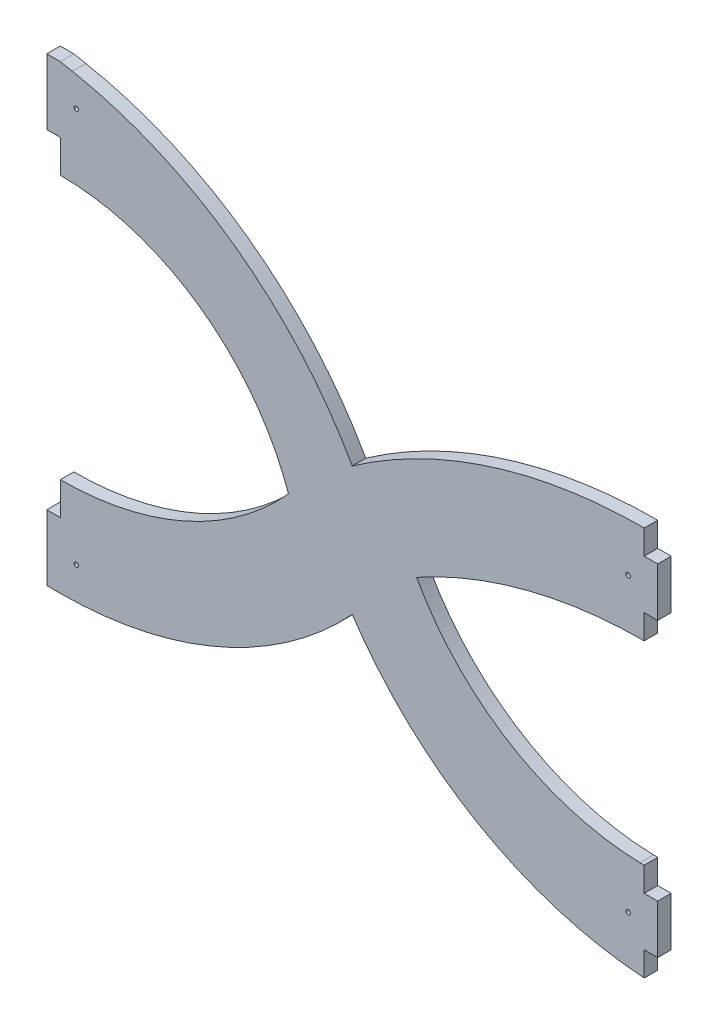
SolidWorks part; units mm, degrees
ref_plane "Front Plane" through (0, 0, 0) normal (0, 0, 1) x (1, 0, 0)
ref_plane "Top Plane" through (0, 0, 0) normal (0, 1, 0) x (1, 0, 0)
ref_plane "Right Plane" through (0, 0, 0) normal (1, 0, 0) x (0, 0, -1)
sketch "Sketch1" plane through (0, 0, 0) normal (0, 0, 1) x (1, 0, 0)
  line L1 (-141.9798, 90.4351) -> (99.3202, 90.4351)
  line L2 (-141.9798, 90.4351) -> (-141.9798, -107.6849)
  line L3 (-141.9798, -107.6849) -> (99.3202, -107.6849)
  line L4 (99.3202, 90.4351) -> (99.3202, -107.6849)
  dimension "D1" = 241.3
  dimension "D2" = 198.12
extrude "Boss-Extrude1" add sketch "Sketch1" along normal blind 5.334
sketch "Sketch2" plane through (0, 0, 5.334) normal (0, 0, 1) x (1, 0, 0)
  line L0 (99.3202, -107.6849) -> (99.3202, 90.4351) construction
  line L1 (99.3202, -107.6849) -> (93.9862, -107.6849)
  line L2 (99.3202, -107.6849) -> (99.3202, -98.0329)
  line L3 (99.3202, -98.0329) -> (93.9862, -98.0329)
  line L4 (93.9862, -107.6849) -> (93.9862, -98.0329)
  line L5 (99.3202, -78.7289) -> (93.9862, -78.7289)
  line L7 (93.9862, 17.2831) -> (99.3202, 17.2831)
  line L8 (93.9862, 17.2831) -> (93.9862, -78.7289)
  line L9 (93.9862, 36.5871) -> (93.9862, 17.2831) construction
  line L10 (99.3202, 90.4351) -> (93.9862, 90.4351)
  line L11 (99.3202, 90.4351) -> (99.3202, 36.5871)
  line L12 (99.3202, 36.5871) -> (93.9862, 36.5871)
  line L13 (93.9862, 90.4351) -> (93.9862, 36.5871)
  line L16 (99.3202, 17.2831) -> (99.3202, -78.7289)
  line L18 (93.9862, -78.7289) -> (93.9862, -98.0329) construction
  dimension "D1" = 5.334
  dimension "D3" = 19.304
  dimension "D4" = 9.652
  dimension "D5" = 19.304
  dimension "D2" = 96.012
extrude "Cut-Extrude1" cut sketch "Sketch2" against normal through all
sketch "Sketch3" plane through (0, 0, 5.334) normal (0, 0, 1) x (1, 0, 0)
  line L1 (-141.9798, -107.6849) -> (-136.6458, -107.6849)
  line L2 (-141.9798, -107.6849) -> (-141.9798, -91.4289)
  line L3 (-141.9798, -91.4289) -> (-136.6458, -91.4289)
  line L4 (-136.6458, -107.6849) -> (-136.6458, -91.4289)
  line L5 (-141.9798, 90.4351) -> (-141.9798, -107.6849) construction
  line L6 (-136.6458, -65.5209) -> (-141.9798, -65.5209)
  line L7 (-136.6458, -65.5209) -> (-136.6458, 64.5271)
  line L8 (-136.6458, 64.5271) -> (-141.9798, 64.5271)
  line L9 (-141.9798, -65.5209) -> (-141.9798, 64.5271)
  line L10 (-136.6458, -65.5209) -> (-136.6458, -91.4289) construction
  line L11 (-136.6458, 64.5271) -> (-136.6458, 90.4351) construction
  line L12 (93.9862, 90.4351) -> (-141.9798, 90.4351) construction
  dimension "D1" = 16.256
  dimension "D2" = 25.908
  dimension "D3" = 25.908
  dimension "D4" = 5.334
extrude "Cut-Extrude2" cut sketch "Sketch3" against normal through all
sketch "Sketch5" plane through (0, 0, 5.334) normal (0, 0, 1) x (1, 0, 0)
  line L0 (-136.6458, -91.4289) -> (93.9862, -107.6849) construction
  line L1 (-136.6458, -91.4289) -> (93.9862, -107.6849)
  line L2 (-136.6458, -91.4289) -> (-136.6458, -146.6044)
  line L3 (93.9862, -107.6849) -> (93.9862, -162.8604)
  line L4 (-136.6458, -146.6044) -> (93.9862, -162.8604)
extrude "Cut-Extrude5" cut sketch "Sketch5" against normal through all
sketch "Sketch6" plane through (0, 0, 5.334) normal (0, 0, 1) x (1, 0, 0)
  line L0 (-136.6458, 64.5271) -> (-136.6458, 90.4351) construction
  line L1 (93.9862, 90.4351) -> (-141.9798, 90.4351) construction
  line L2 (93.9862, 36.5871) -> (93.9862, 46.2391) construction
  line L3 (93.9862, 90.4351) -> (93.9862, 36.5871) construction
  line L4 (-136.6458, 90.4351) -> (93.9862, 46.2391)
  line L5 (-136.6458, 90.4351) -> (-136.6458, 134.6311)
  line L6 (93.9862, 46.2391) -> (93.9862, 90.4351)
  line L7 (-136.6458, 134.6311) -> (93.9862, 90.4351)
  dimension "D1" = 9.652
extrude "Cut-Extrude6" cut sketch "Sketch6" against normal through all
sketch "Sketch7" plane through (0, 0, 5.334) normal (0, 0, 1) x (1, 0, 0)
  line L0 (-21.3298, 68.3371) -> (-21.3298, -99.5569) construction
  line L1 (-136.6458, 90.4351) -> (93.9862, 46.2391) construction
  line L2 (93.9862, -107.6849) -> (-136.6458, -91.4289) construction
  line L3 (93.9862, -30.7229) -> (-136.6458, -0.4969) construction
  line L4 (93.9862, 17.2831) -> (93.9862, -78.7289) construction
  line L5 (-136.6458, -65.5209) -> (-136.6458, 64.5271) construction
  line L6 (-136.6458, 64.5271) -> (-136.6458, 51.5731) construction
  line L7 (-136.6458, -65.5209) -> (-136.6458, -52.5669) construction
  line L8 (93.9862, 17.2831) -> (93.9862, 7.6311) construction
  line L9 (93.9862, -78.7289) -> (93.9862, -69.0769) construction
  line L10 (-136.6458, 64.5271) -> (-131.8569, 89.5174) construction
  line L11 (93.9862, 36.5871) -> (93.9862, 46.2391) construction
  line L12 (-131.8569, 89.5174) -> (93.9862, 46.2391)
  line L13 (-136.6458, -65.5209) -> (-136.6458, -91.4289) construction
  line L14 (93.9862, -98.0329) -> (93.3092, -107.6372) construction
  line L15 (-136.6458, -91.4289) -> (93.3092, -107.6372)
  circle A0 centre (-21.3298, -15.6099) radius 25.4 construction
  arc A1 (93.9862, 7.6311) -> (4.0702, -15.6099) centre (93.9862, -177.9253) ccw
  arc A2 (4.0702, -15.6099) -> (92.3478, -69.0769) centre (94.8631, 34.6856) ccw
  arc A3 (92.3478, -69.0769) -> (93.9862, 7.6311) centre (93.2775, -30.7253) ccw
  arc A4 (-136.6458, 51.5731) -> (-46.5144, -12.3093) centre (-136.6458, -43.9511) cw
  arc A5 (-136.6458, -52.5669) -> (-46.5144, -12.3093) centre (-136.6458, 68.4578) ccw
  arc A6 (-136.6458, 51.5731) -> (-136.6458, -52.5669) centre (-136.6458, -0.4969) ccw
  arc A7 (-131.8569, 89.5174) -> (-21.3298, 9.7901) centre (-162.252, -69.0961) cw
  arc A8 (93.9862, 46.2391) -> (-21.3298, 9.7901) centre (93.9862, -154.4017) ccw
  arc A9 (-136.6458, -91.4289) -> (-21.3298, -41.0099) centre (-136.6458, 65.6533) ccw
  arc A10 (93.3092, -107.6372) -> (-21.3298, -41.0099) centre (103.8923, 42.5097) cw
extrude "Cut-Extrude7" cut sketch "Sketch7" against normal through all
sketch "Sketch8" plane through (0, 0, 5.334) normal (0, 0, 1) x (1, 0, 0)
  line L0 (-141.9798, 90.4351) -> (-141.9798, 64.5271) construction
  line L1 (-141.9798, 77.4811) -> (-82.7249, 77.4811) construction
  line L2 (-141.9798, 77.4811) -> (-141.9798, -78.4749) construction
  line L3 (-141.9798, -65.5209) -> (-141.9798, -91.4289) construction
  line L4 (-141.9798, -0.4969) -> (-61.4833, -0.4969) construction
  circle A0 centre (-130.2958, 77.4811) radius 0.889
  circle A1 centre (-130.2958, -78.4749) radius 0.889
  point P2 (-141.9798, 77.4811)
  dimension "D3" = 1.778
  dimension "D1" = 11.684
  dimension "D2" = 0
extrude "Cut-Extrude8" cut sketch "Sketch8" against normal through all
sketch "Sketch9" plane through (0, 0, 5.334) normal (0, 0, 1) x (1, 0, 0)
  line L0 (99.3202, 26.9351) -> (60.8503, 26.9351) construction
  line L1 (99.3202, 17.2831) -> (99.3202, 36.5871) construction
  line L2 (99.3202, -88.3809) -> (53.0576, -88.3809) construction
  line L3 (99.3202, -98.0329) -> (99.3202, -78.7289) construction
  line L4 (99.3202, 26.9351) -> (99.3202, -88.3809) construction
  line L5 (99.3202, -30.7229) -> (41.8715, -30.7229) construction
  line L6 (93.9862, 46.2391) -> (93.9862, 36.5871) construction
  circle A0 centre (87.6362, 26.9351) radius 0.889
  circle A1 centre (87.6362, -88.3809) radius 0.889
  dimension "D1" = 1.778
  dimension "D2" = 0
  dimension "D3" = 6.35
extrude "Cut-Extrude9" cut sketch "Sketch9" against normal through all
equation "\"MDF\"= .21in"
equation "\"Foamcore\"= .13in"
equation "\"Gmaterial\"= \"MDF\""
equation "\"D1@Boss-Extrude1\"=\"MDF\""
equation "\"D1@Sketch2\"=\"MDF\""
equation "\"D4@Sketch3\"=\"MDF\""
equation "\"D1@Sketch8\"=0.25+\"MDF\""
